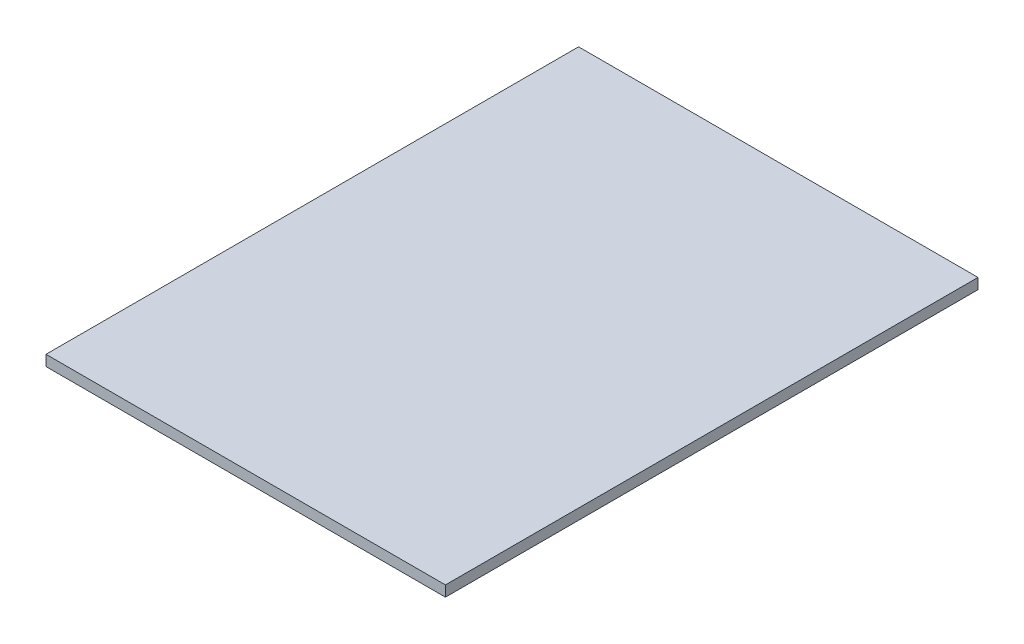
SolidWorks part; units mm, degrees
ref_plane "Front Plane" through (0, 0, 0) normal (0, 0, 1) x (1, 0, 0)
ref_plane "Top Plane" through (0, 0, 0) normal (0, 1, 0) x (1, 0, 0)
ref_plane "Right Plane" through (0, 0, 0) normal (1, 0, 0) x (0, 0, -1)
sketch "Sketch1" plane through (0, 0, 0) normal (0, 1, 0) x (1, 0, 0)
  line L1 (-37.5, 50) -> (37.5, 50)
  line L2 (-37.5, 50) -> (-37.5, -50)
  line L3 (-37.5, -50) -> (37.5, -50)
  line L4 (37.5, 50) -> (37.5, -50)
  line L5 (-37.5, 50) -> (37.5, -50) construction
  line L6 (-37.5, -50) -> (37.5, 50) construction
  point P0 (0, 0)
  dimension "D1" = 75
  dimension "D2" = 100
extrude "Boss-Extrude1" add sketch "Sketch1" along normal blind 2
